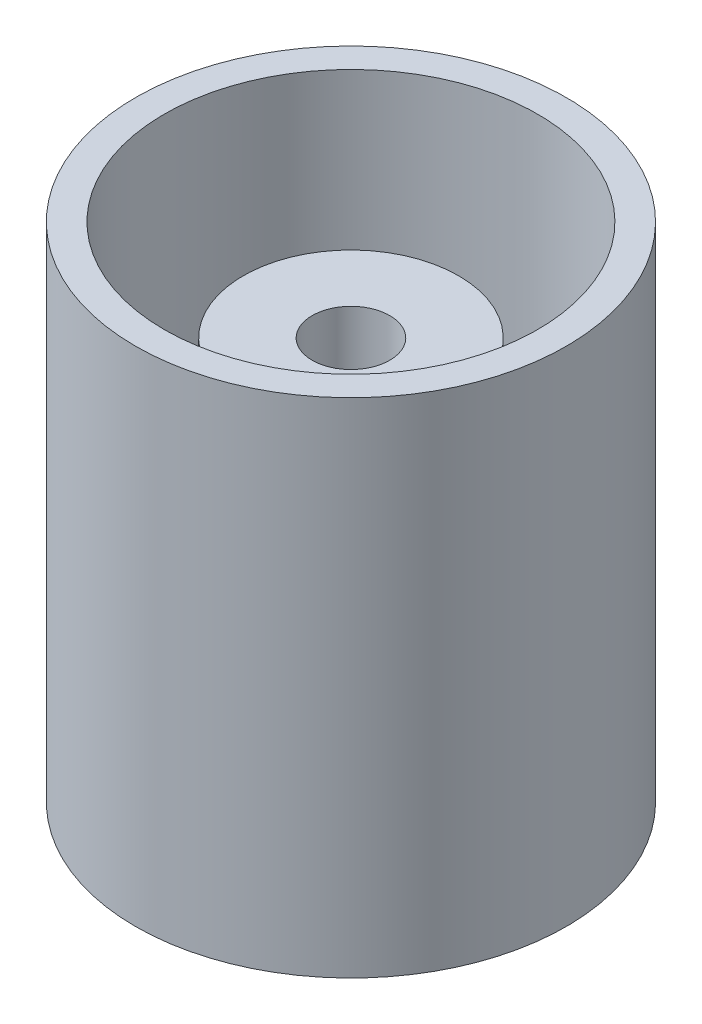
SolidWorks part; units mm, degrees
ref_plane "Front Plane" through (0, 0, 0) normal (0, 0, 1) x (1, 0, 0)
ref_plane "Top Plane" through (0, 0, 0) normal (0, 1, 0) x (1, 0, 0)
ref_plane "Right Plane" through (0, 0, 0) normal (1, 0, 0) x (0, 0, -1)
sketch "Sketch1" plane through (0, 0, 0) normal (0, 1, 0) x (1, 0, 0)
  circle A0 centre (0, 0) radius 15
  dimension "D1" = 30
extrude "Boss-Extrude1" add sketch "Sketch1" along normal blind 15
sketch "Sketch2" plane through (0, 15, 0) normal (0, 1, 0) x (1, 0, 0)
  circle A0 centre (0, 0) radius 7.5
extrude "Boss-Extrude2" add sketch "Sketch2" along normal blind 13
sketch "Sketch3" plane through (0, 15, 0) normal (0, 1, 0) x (1, 0, 0)
  circle A0 centre (0, 0) radius 13
  circle A1 centre (0, 0) radius 15 construction
  circle A2 centre (0, 0) radius 15
  dimension "D1" = 2
extrude "Boss-Extrude4" add sketch "Sketch3" along normal blind 20
sketch "Sketch4" plane through (0, 28, 0) normal (0, 1, 0) x (1, 0, 0)
  circle A0 centre (0, 0) radius 2.7
extrude "Cut-Extrude1" cut sketch "Sketch4" against normal blind 30
